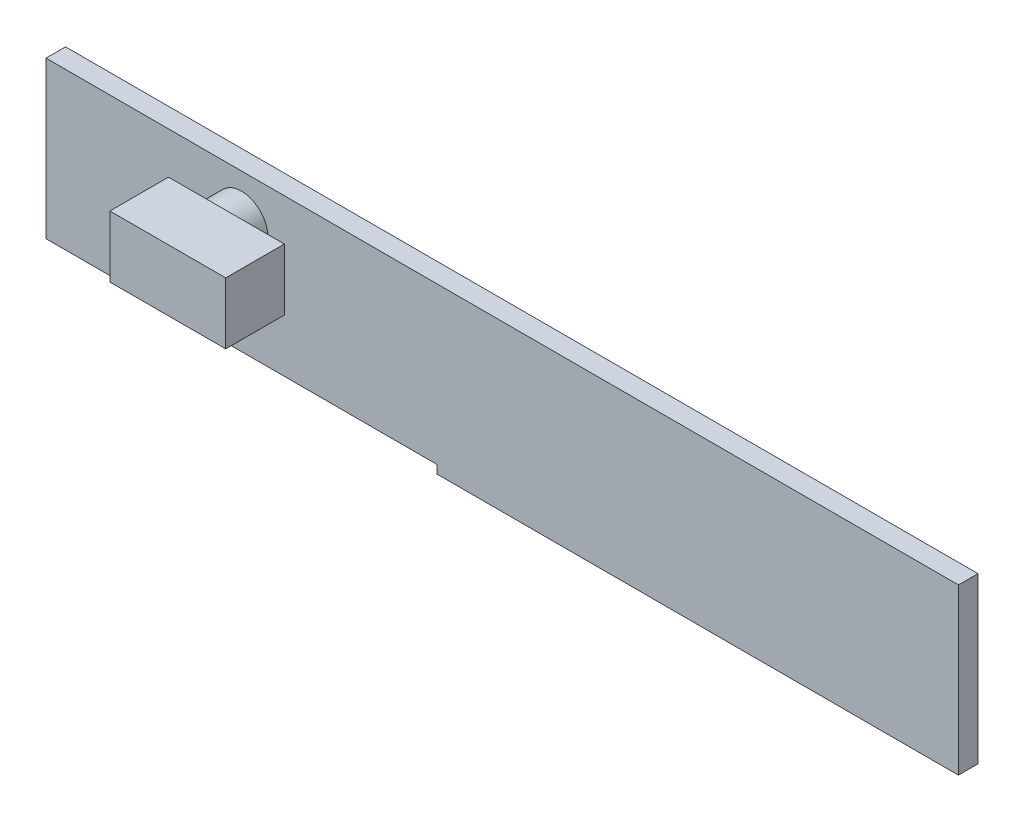
SolidWorks part; units mm, degrees
ref_plane "Front Plane" through (0, 0, 0) normal (0, 0, 1) x (1, 0, 0)
ref_plane "Top Plane" through (0, 0, 0) normal (0, 1, 0) x (1, 0, 0)
ref_plane "Right Plane" through (0, 0, 0) normal (1, 0, 0) x (0, 0, -1)
sketch "Sketch2" plane through (0, 0, 0) normal (0, 0, 1) x (1, 0, 0)
  line L1 (-47.8692, 21.2481) -> (206.1308, 21.2481)
  line L2 (-47.8692, 21.2481) -> (-47.8692, 8.5481)
  line L3 (-47.8692, 8.5481) -> (206.1308, 8.5481)
  line L4 (206.1308, 21.2481) -> (206.1308, 8.5481)
  dimension "D1" = 12.7
  dimension "D2" = 254
extrude "Boss-Extrude1" add sketch "Sketch2" along normal blind 101.6
sketch "Sketch3" plane through (0, 21.2481, 0) normal (0, 1, 0) x (1, 0, 0)
  circle A0 centre (79.1308, -28.4831) radius 17.1408
extrude "Boss-Extrude2" add sketch "Sketch3" along normal blind 19.05
sketch "Sketch4" plane through (0, 40.2981, 0) normal (0, 1, 0) x (1, 0, 0)
  line L1 (50.7675, -8.111) -> (126.0034, -8.111)
  line L2 (50.7675, -8.111) -> (50.7675, -48.0661)
  line L3 (50.7675, -48.0661) -> (126.0034, -48.0661)
  line L4 (126.0034, -8.111) -> (126.0034, -48.0661)
extrude "Boss-Extrude3" add sketch "Sketch4" along normal blind 38.1
scale "Scale2" scale about centroid uniform scaling yes scale factor 0.00375
move or copy body "rotate" bodies to move or copy 105 copy no rotation origin (0, 33.6669, 26.5501) rotation axis (1, 0, 0) rotation angle 90
move or copy body "-4 x" bodies to move or copy 106 copy no translate (-101.6, 0, 0)
move or copy body "-2 y" bodies to move or copy 117 copy no translate (0, -55.88, 0)
move or copy body "-2.1z" bodies to move or copy 121 copy no translate (0, 0, -30.48)
sketch "Sketch6" plane through (0, -39.7871, 0) normal (0, 1, 0) x (1, 0, 0)
  line L1 (-19.6967, 11.0887) -> (-18.4267, 11.0887)
  line L2 (-19.6967, 11.0887) -> (-19.6967, 11.0411)
  line L3 (-19.6967, 11.0411) -> (-18.4267, 11.0411)
  line L4 (-18.4267, 11.0887) -> (-18.4267, 11.0411)
  dimension "D1" = 1.27
extrude "Boss-Extrude6" add sketch "Sketch6" against normal blind 0.4013
